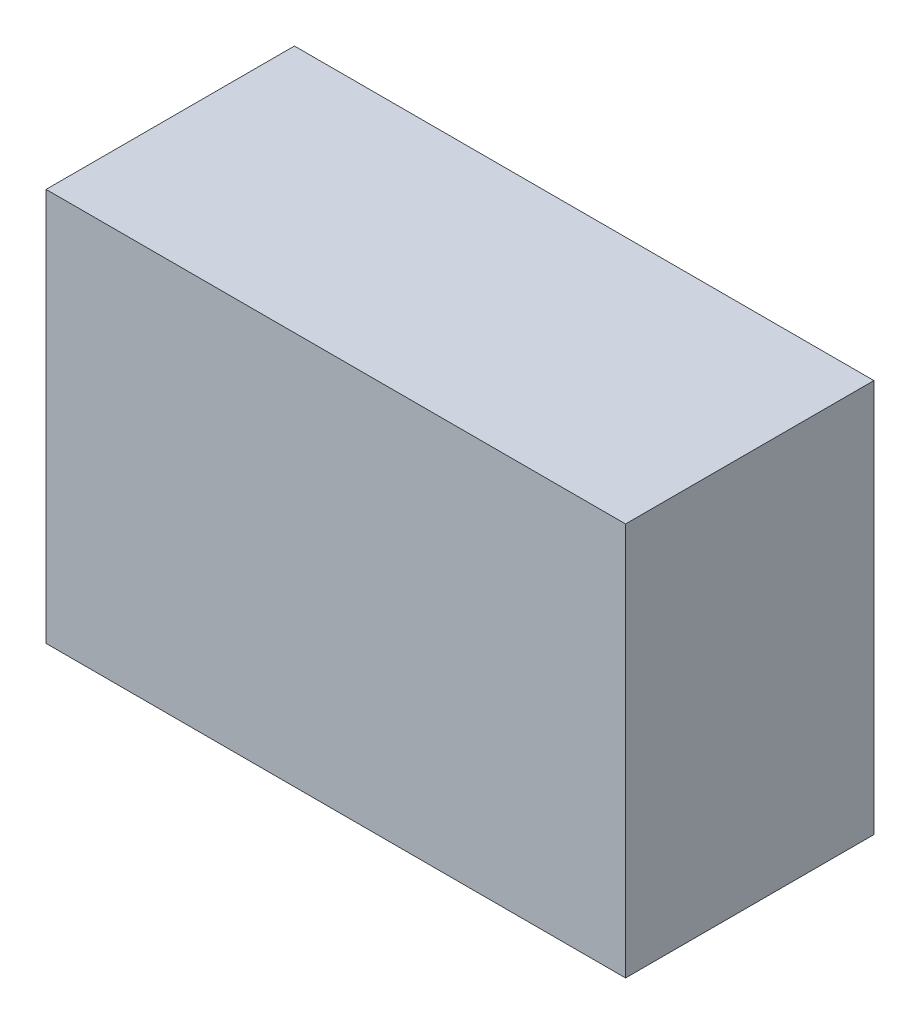
SolidWorks part; units mm, degrees
ref_plane "Front Plane" through (0, 0, 0) normal (0, 0, 1) x (1, 0, 0)
ref_plane "Top Plane" through (0, 0, 0) normal (0, 1, 0) x (1, 0, 0)
ref_plane "Right Plane" through (0, 0, 0) normal (1, 0, 0) x (0, 0, -1)
sketch "Sketch1" plane through (0, 0, 0) normal (0, 0, 1) x (1, 0, 0)
  line L0 (-355.6, 241.3) -> (355.6, -241.3) construction
  line L1 (-355.6, 241.3) -> (355.6, 241.3)
  line L2 (-355.6, 241.3) -> (-355.6, -241.3)
  line L3 (-355.6, -241.3) -> (355.6, -241.3)
  line L4 (355.6, 241.3) -> (355.6, -241.3)
  dimension "D1" = 711.2
  dimension "D2" = 482.6
extrude "Boss-Extrude1" add sketch "Sketch1" along normal mid plane 304.8
